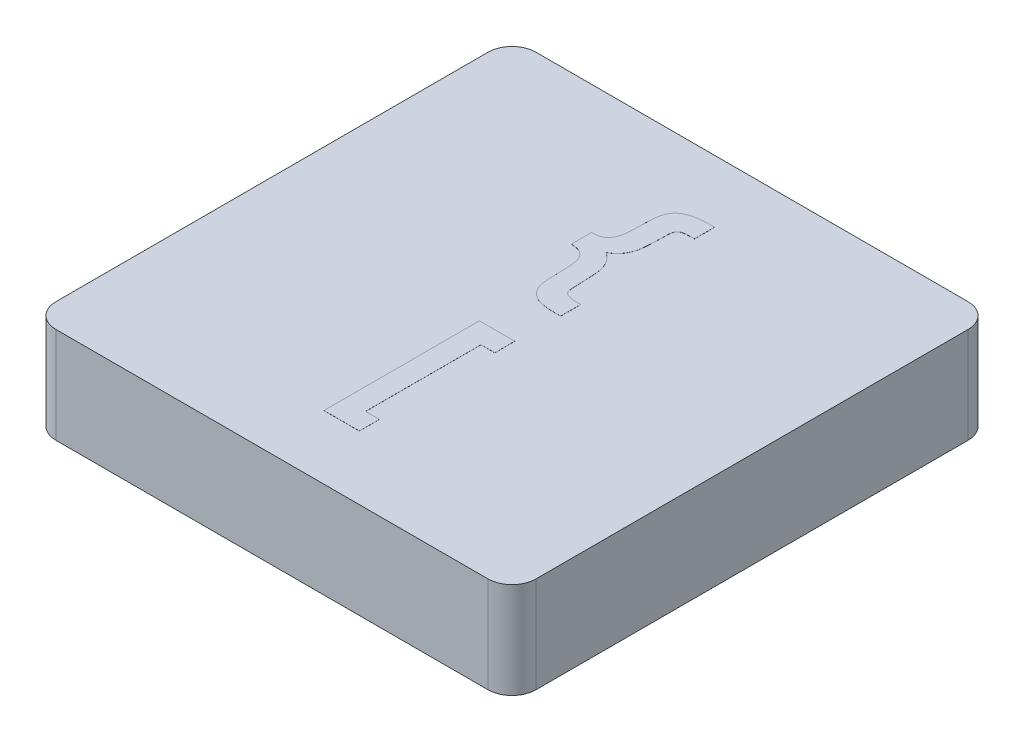
SolidWorks part; units mm, degrees
ref_plane "Front Plane" through (0, 0, 0) normal (0, 0, 1) x (1, 0, 0)
ref_plane "Top Plane" through (0, 0, 0) normal (0, 1, 0) x (1, 0, 0)
ref_plane "Right Plane" through (0, 0, 0) normal (1, 0, 0) x (0, 0, -1)
sketch "Sketch1" plane through (0, 0, 0) normal (0, 1, 0) x (1, 0, 0)
  line L0 (0, 0) -> (12.7, 0)
  line L1 (12.7, 0) -> (12.7, 12.7)
  line L2 (12.7, 12.7) -> (0, 12.7)
  line L3 (0, 12.7) -> (0, 0)
  dimension "D1" = 12.7
  dimension "D2" = 12.7
extrude "Boss-Extrude1" add sketch "Sketch1" along normal blind 2.54
fillet "Fillet1" radius 0.635 4 edges at (0, 1.27, -12.7) (12.7, 1.27, -12.7) (12.7, 1.27, 0) (0, 1.27, 0)
shell "Shell1" thickness 0.635 removed face at (6.35, 0, -6.35)
sketch "Sketch2" plane through (0, 1.905, 0) normal (0, -1, 0) x (-1, 0, 0)
  line L0 (-0.635, 6.35) -> (-12.065, 6.35) construction
  line L1 (-0.635, 12.065) -> (-0.635, 0.635) construction
  line L2 (-12.065, 0.635) -> (-12.065, 12.065) construction
  line L3 (-6.35, 0.635) -> (-6.35, 12.065) construction
  line L4 (-0.635, 0.635) -> (-12.065, 0.635) construction
  line L5 (-12.065, 12.065) -> (-0.635, 12.065) construction
  circle A0 centre (-6.35, 6.35) radius 2.54
  dimension "D1" = 5.08
extrude "Boss-Extrude2" add sketch "Sketch2" along normal up to surface (1.905 mm away) up to face at (6.35, 0, -6.35)
sketch "Sketch4" plane through (0, 2.54, 0) normal (0, 1, 0) x (1, 0, 0)
  line L0 (0, 12.065) -> (0, 0.635) construction
  line L1 (12.065, 12.7) -> (0.635, 12.7) construction
  line L2 (0.635, 0) -> (12.065, 0) construction
  text T0 "<b>[</b>"
  text T1 "<b>{</b>"
  dimension "D1" = 5.461
  dimension "D2" = 5.715
  dimension "D3" = 4.826
  dimension "D4" = 2.54
extrude "Boss-Extrude4" add sketch "Sketch4" along normal blind 0.0025
